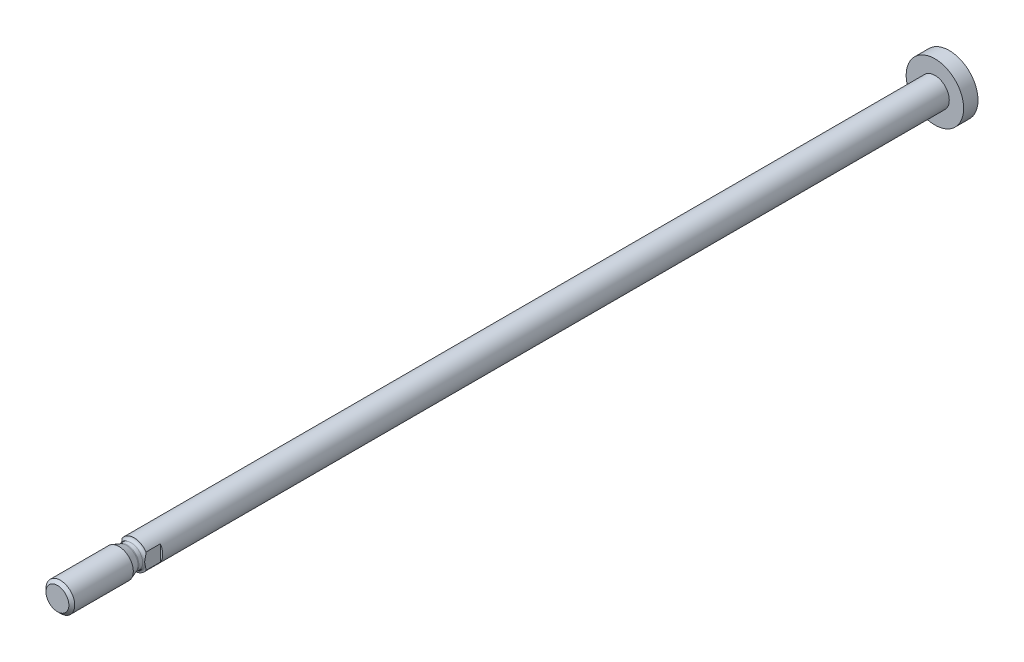
SolidWorks part; units mm, degrees
ref_plane "Ebene vorne" through (0, 0, 0) normal (0, 0, 1) x (1, 0, 0)
ref_plane "Ebene oben" through (0, 0, 0) normal (0, 1, 0) x (1, 0, 0)
ref_plane "Ebene rechts" through (0, 0, 0) normal (1, 0, 0) x (0, 0, -1)
sketch "Skizze1" plane through (0, 0, 0) normal (1, 0, 0) x (0, 0, -1)
  line L0 (-5, 0) -> (-5, 3)
  line L1 (-5, 3) -> (162.3, 3)
  line L2 (162.3, 3) -> (162.3, 6)
  line L3 (162.3, 6) -> (165.3, 6)
  line L4 (165.3, 6) -> (165.3, 0)
  line L5 (165.3, 0) -> (-5, 0)
  line L6 (165.3, 0) -> (-5, 0) construction
revolve "Rotation1" add sketch "Skizze1" angle 360 about L6 reverse direction yes
sketch "Skizze2" plane through (0, 0, 0) normal (1, 0, 0) x (0, 0, -1)
  line L0 (-21, 0) -> (-21, 2.3865)
  line L1 (-21, 2.3865) -> (-20.3865, 3)
  line L2 (-20.3865, 3) -> (-8.1485, 3)
  line L3 (-8.1485, 3) -> (-6.5994, 2.4362)
  line L4 (-6.3942, 2.4) -> (-5.6, 2.4)
  line L5 (-5, 3) -> (-4, 3)
  line L6 (-4, 3) -> (-4, 0)
  line L7 (-4, 0) -> (-21, 0)
  line L8 (-4, 0) -> (-21, 0) construction
  arc A0 (-6.5994, 2.4362) -> (-6.3942, 2.4) centre (-6.3942, 3) ccw
  arc A1 (-5.6, 2.4) -> (-5, 3) centre (-5.6, 3) ccw
revolve "Rotation2" add sketch "Skizze2" angle 360 about L8 reverse direction yes
cosmetic thread "Gewindedarstellung1" parameters "D1"=12.8515, "D2"=4.773
ref_plane "Ebene1" through (0, 0, 5) normal (0, 0, 1) x (1, 0, 0)
ref_plane "Ebene2" through (0, 0, 2) normal (0, 0, 1) x (1, 0, 0)
sketch "Skizze3" plane through (0, 0, 2) normal (0, 0, 1) x (1, 0, 0)
  line L0 (-5, 10) -> (-5, -5)
  line L1 (-5, -5) -> (-2.5, -5)
  line L2 (-2.5, -5) -> (-2.5, 5)
  line L3 (-2.5, 5) -> (2.5, 5)
  line L4 (2.5, 5) -> (2.5, -5)
  line L5 (2.5, -5) -> (5, -5)
  line L6 (5, -5) -> (5, 10)
  line L7 (5, 10) -> (-5, 10)
extrude "Schnitt-Linear austragen1" cut sketch "Skizze3" along normal blind 4
ref_plane "Ebene3" through (0, 0, -339) normal (0, 0, 1) x (1, 0, 0)
ref_plane "Ebene4" through (0, 0, 16) normal (0, 0, 1) x (1, 0, 0)
ref_plane "Ebene5" through (0, 0, 11.2) normal (0, 0, 1) x (1, 0, 0)
ref_plane "FDT_KSAUFSATZ XY" through (0, 0, 11.2) normal (0, 0, 1) x (1, 0, 0)
ref_plane "FDT_KSAUFSATZ XZ" through (0, 0, 0) normal (0, 1, 0) x (1, 0, 0)
ref_plane "FDT_KSAUFSATZ YZ" through (0, 0, 0) normal (-1, 0, 0) x (0, 0, 1)
ref_axis "FDT_KSAUFSATZ X" through (80.9, 0, 11.2) along (-1, 0, 0)
ref_axis "FDT_KSAUFSATZ Y" through (0, 50, 11.2) along (0, -1, 0)
ref_axis "FDT_KSAUFSATZ Z" through (0, 0, 80.9) along (0, 0, -1)
sketch3d "FDT_KSAUFSATZ"
  point P0 (0, 0, 11.2)
ref_plane "FDT_NUT XY" through (0, 0, 11.2) normal (0, 0, 1) x (1, 0, 0)
ref_plane "FDT_NUT XZ" through (0, 0, 0) normal (0, 1, 0) x (1, 0, 0)
ref_plane "FDT_NUT YZ" through (0, 0, 0) normal (-1, 0, 0) x (0, 0, 1)
ref_axis "FDT_NUT X" through (80.9, 0, 11.2) along (-1, 0, 0)
ref_axis "FDT_NUT Y" through (0, 50, 11.2) along (0, -1, 0)
ref_axis "FDT_NUT Z" through (0, 0, 80.9) along (0, 0, -1)
sketch3d "FDT_NUT"
  point P0 (0, 0, 11.2)
ref_plane "KS XY" through (0, 0, 0) normal (0, 0, -1) x (-1, 0, 0)
ref_plane "KS XZ" through (0, 0, 0) normal (0, 1, 0) x (1, 0, 0)
ref_plane "KS YZ" through (0, 0, 0) normal (1, 0, 0) x (0, 0, -1)
ref_axis "KS X" through (-80.9, 0, 0) along (1, 0, 0)
ref_axis "KS Y" through (0, 50, 0) along (0, -1, 0)
ref_axis "KS Z" through (0, 0, -80.9) along (0, 0, 1)
sketch3d "KS"
  point P0 (0, 0, 0)
ref_plane "NUT1 XY" through (0, 0, 16) normal (0, 0, 1) x (1, 0, 0)
ref_plane "NUT1 XZ" through (0, 0, 0) normal (0, -1, 0) x (-1, 0, 0)
ref_plane "NUT1 YZ" through (0, 0, 0) normal (1, 0, 0) x (0, 0, -1)
ref_axis "NUT1 X" through (-80.9, 0, 16) along (1, 0, 0)
ref_axis "NUT1 Y" through (0, -50, 16) along (0, 1, 0)
ref_axis "NUT1 Z" through (0, 0, 80.9) along (0, 0, -1)
sketch3d "NUT1"
  point P0 (0, 0, 16)
sketch "Sketch1" plane through (0, 0, 0) normal (0, 1, 0) x (1, 0, 0)
  line L0 (-2.3865, -21) -> (2.3865, -21) construction
  point P0 (0, -41)
  dimension "D1" = 20
